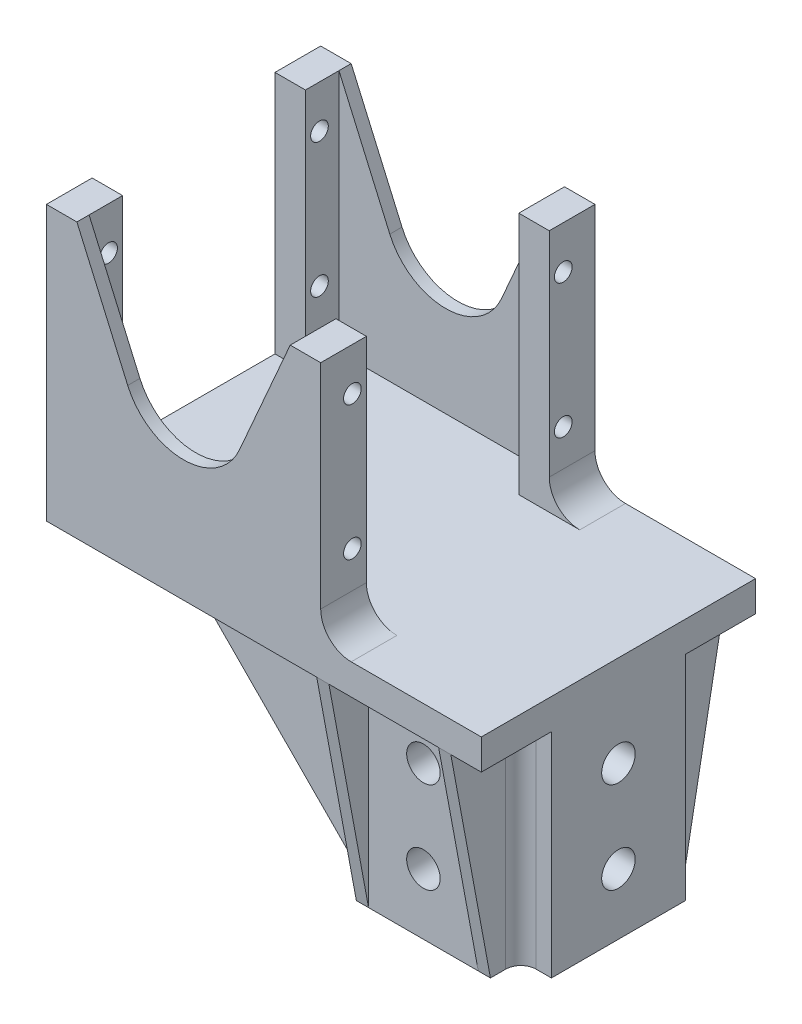
SolidWorks part; units mm, degrees
material "PLA"
ref_plane "Front Plane" through (0, 0, 0) normal (0, 0, 1) x (1, 0, 0)
ref_plane "Top Plane" through (0, 0, 0) normal (0, 1, 0) x (1, 0, 0)
ref_plane "Right Plane" through (0, 0, 0) normal (1, 0, 0) x (0, 0, -1)
sketch "Sketch2" plane through (0, 0, 0) normal (0, 0, 1) x (1, 0, 0)
  line L0 (12.8375, 22.5) -> (17.8375, 22.5) construction
  line L1 (-53.5125, 22.5) -> (17.8375, 22.5) construction
  line L2 (-17.8375, 22.5) -> (-17.8375, -22.5) construction
  line L3 (-53.5125, -22.5) -> (17.8375, -22.5)
  line L4 (17.8375, 22.5) -> (17.8375, -22.5) construction
  line L5 (-17.8375, 22.5) -> (17.8375, -22.5) construction
  line L6 (-17.8375, -22.5) -> (17.8375, 22.5) construction
  line L7 (-48.5125, 22.5) -> (12.8375, 22.5) construction
  line L8 (-17.8375, 22.5) -> (-17.8375, -17.5) construction
  line L9 (-48.5125, -17.5) -> (12.8375, -17.5) construction
  line L10 (12.8375, 22.5) -> (12.8375, -17.5) construction
  line L11 (-17.8375, 22.5) -> (12.8375, -17.5) construction
  line L12 (-17.8375, -17.5) -> (12.8375, 22.5) construction
  line L14 (-17.8375, -17.5) -> (-48.5125, 22.5) construction
  line L15 (-17.8375, 22.5) -> (-48.5125, -17.5) construction
  line L16 (-17.8375, -22.5) -> (-53.5125, 22.5) construction
  line L17 (-17.8375, 22.5) -> (-53.5125, -22.5) construction
  line L18 (-48.5125, 22.5) -> (-48.5125, -17.5)
  line L19 (-53.5125, 22.5) -> (-53.5125, -22.5)
  line L20 (-48.5125, 22.5) -> (-53.5125, 22.5)
  line L22 (-8.5125, -17.5) -> (-8.5125, 22.5)
  line L23 (-8.5125, 22.5) -> (-13.5125, 22.5)
  line L24 (-13.5125, 22.5) -> (-13.5125, -17.5)
  line L26 (17.8375, -17.5) -> (17.8375, -22.5)
  line L27 (-48.5125, -17.5) -> (-13.5125, -17.5)
  line L28 (-8.5125, -17.5) -> (17.8375, -17.5)
  point P4 (0, 0)
  point P8 (-2.5, 2.5)
  point P14 (-33.175, 2.5)
  point P15 (-35.675, 0)
  dimension "D1" = 5
  dimension "D2" = 40
  dimension "D3" = 26.35
  dimension "D4" = 5
  dimension "D5" = 35
  dimension "D6" = 5
extrude "Boss-Extrude1" add sketch "Sketch2" along normal blind 45
sketch "Sketch3" plane through (-53.5125, 0, 0) normal (1, 0, 0) x (0, 0, -1)
  line L0 (-5.2, 22.5) -> (-5.2, -22.5) construction
  line L2 (-39.8, 22.5) -> (-39.8, -22.5) construction
  line L4 (-37.5, 22.5) -> (-7.5, 22.5)
  line L5 (-37.5, 22.5) -> (-37.5, -17.5)
  line L6 (-37.5, -17.5) -> (-7.5, -17.5)
  line L7 (-7.5, 22.5) -> (-7.5, -17.5)
  line L8 (-37.5, 22.5) -> (-7.5, -17.5) construction
  line L9 (-37.5, -17.5) -> (-7.5, 22.5) construction
  line L10 (-45, 22.5) -> (0, 22.5) construction
  line L11 (-39.8, 15.5) -> (-5.2, 15.5) construction
  line L12 (-39.8, -6.5) -> (-5.2, -6.5) construction
  line L13 (-45, -22.5) -> (0, -22.5) construction
  circle A2 centre (-5.2, 15.5) radius 1.25 construction
  circle A3 centre (-5.2, -6.5) radius 1.25 construction
  circle A4 centre (-39.8, 15.5) radius 1.25 construction
  circle A5 centre (-39.8, -6.5) radius 1.25 construction
  point P10 (-22.5, 2.5)
  dimension "D4" = 2.3
  dimension "D7" = 2.5
  dimension "D5" = 2.5
  dimension "D6" = 2.5
  dimension "D9" = 2.5
  dimension "D8" = 22
  dimension "D1" = 30
  dimension "D2" = 5
  dimension "D3" = 2.3
  dimension "D10" = 11
extrude "Cut-Extrude1" cut sketch "Sketch3" along normal through all
sketch "Sketch4" plane through (0, -22.5, 0) normal (0, -1, 0) x (1, 0, 0)
  line L0 (-53.5125, 22.5) -> (17.8375, 22.5) construction
  line L1 (17.8375, 45) -> (17.8375, 0) construction
  line L3 (-53.5125, 45) -> (-53.5125, 0) construction
  line L10 (-8.4125, 32.75) -> (12.0875, 32.75)
  line L11 (-8.4125, 32.75) -> (-8.4125, 12.25)
  line L12 (-8.4125, 12.25) -> (12.0875, 12.25)
  line L13 (12.0875, 32.75) -> (12.0875, 12.25)
  line L14 (-8.4125, 32.75) -> (12.0875, 12.25) construction
  line L15 (-8.4125, 12.25) -> (12.0875, 32.75) construction
  line L16 (-14.1625, 38.5) -> (17.8375, 38.5)
  line L17 (-14.1625, 38.5) -> (-14.1625, 6.5)
  line L18 (-14.1625, 6.5) -> (17.8375, 6.5)
  line L19 (17.8375, 38.5) -> (17.8375, 6.5)
  line L20 (-14.1625, 38.5) -> (17.8375, 6.5) construction
  line L21 (-14.1625, 6.5) -> (17.8375, 38.5) construction
  circle A0 centre (1.8375, 22.5) radius 2.5
  point P18 (1.8375, 22.5)
  point P23 (1.8375, 22.5)
  dimension "D1" = 5
  dimension "D2" = 20.5
  dimension "D3" = 20.5
  dimension "D4" = 32
extrude "Boss-Extrude2" add sketch "Sketch4" along normal blind 35 contours L19 L16 L17 L18 L10 L13 L12 L11 region at (1.8375, -22.5, 38.0475)
sketch "Sketch5" plane through (0, 0, 38.5) normal (0, 0, 1) x (1, 0, 0)
  line L0 (1.8375, -22.5) -> (1.8375, -57.5) construction
  line L3 (-14.1625, -22.5) -> (17.8375, -22.5) construction
  line L4 (-14.1625, -57.5) -> (17.8375, -57.5) construction
  circle A0 centre (1.8375, -32.5) radius 2.5 construction
  circle A1 centre (1.8375, -47.5) radius 2.5 construction
  dimension "D2" = 5
  dimension "D3" = 5
  dimension "D4" = 10
  dimension "D1" = 15
sketch "Sketch6" plane through (0, -57.5, 0) normal (0, -1, 0) x (-1, 0, 0)
  line L1 (14.1625, -38.5) -> (9.1625, -38.5)
  line L2 (14.1625, -38.5) -> (14.1625, -33.5)
  line L3 (14.1625, -33.5) -> (9.1625, -33.5)
  line L4 (9.1625, -38.5) -> (9.1625, -33.5)
  line L5 (14.1625, -38.5) -> (9.1625, -33.5) construction
  line L6 (14.1625, -33.5) -> (9.1625, -38.5) construction
  line L7 (-17.8375, -38.5) -> (-12.8375, -38.5)
  line L8 (-17.8375, -38.5) -> (-17.8375, -33.5)
  line L9 (-17.8375, -33.5) -> (-12.8375, -33.5)
  line L10 (-12.8375, -38.5) -> (-12.8375, -33.5)
  line L11 (-17.8375, -38.5) -> (-12.8375, -33.5) construction
  line L12 (-17.8375, -33.5) -> (-12.8375, -38.5) construction
  line L13 (-17.8375, -6.5) -> (-12.8375, -6.5)
  line L14 (-17.8375, -6.5) -> (-17.8375, -11.5)
  line L15 (-17.8375, -11.5) -> (-12.8375, -11.5)
  line L16 (-12.8375, -6.5) -> (-12.8375, -11.5)
  line L17 (-17.8375, -6.5) -> (-12.8375, -11.5) construction
  line L18 (-17.8375, -11.5) -> (-12.8375, -6.5) construction
  line L19 (14.1625, -6.5) -> (9.1625, -6.5)
  line L20 (14.1625, -6.5) -> (14.1625, -11.5)
  line L21 (14.1625, -11.5) -> (9.1625, -11.5)
  line L22 (9.1625, -6.5) -> (9.1625, -11.5)
  line L23 (14.1625, -6.5) -> (9.1625, -11.5) construction
  line L24 (14.1625, -11.5) -> (9.1625, -6.5) construction
  point P4 (11.6625, -36)
  point P6 (-11.8375, -32.5)
  point P11 (-15.3375, -36)
  point P18 (-15.3375, -9)
  point P25 (11.6625, -9)
  dimension "D1" = 5
  dimension "D2" = 5
  dimension "D3" = 5
  dimension "D4" = 5
extrude "Cut-Extrude4" cut sketch "Sketch6" against normal up to surface (35 mm away) up to face at (-8, -22.5, 22.5)
sketch "Sketch9" plane through (0, 0, 33.5) normal (0, 0, 1) x (1, 0, 0)
  line L0 (-14.1625, -57.5) -> (-48.75, -22.5)
  line L1 (-53.5125, -22.5) -> (17.8375, -22.5) construction
  line L2 (-53.5125, -22.5) -> (17.8375, -22.5) construction
rib "Rib1" sketch "Sketch9" sketch "Sketch9" thickness 2 extrusion direction parallel to sketch draft on no parameters "D1"=2
pattern_linear "LPattern1" count 2 spacing 20 along (0, 0, -1) of "Rib1"
sketch "Sketch14" plane through (12.8375, 0, 0) normal (1, 0, 0) x (0, 0, -1)
  line L0 (-6.5, -57.5) -> (0, -22.5)
rib "Rib6" sketch "Sketch14" sketch "Sketch14" thickness 2 extrusion direction parallel to sketch draft on no parameters "D1"=2
sketch "Sketch15" plane through (-9.1625, 0, 0) normal (-1, 0, 0) x (0, 0, 1)
  line L0 (6.5, -57.5) -> (0, -22.5)
rib "Rib7" sketch "Sketch15" sketch "Sketch15" thickness 2 extrusion direction parallel to sketch draft on no parameters "D1"=2
fillet "Fillet2" radius 5 3 edges at (-14.1625, -22.5, 22.5) (1.8375, -22.5, 6.5) (1.8375, -22.5, 38.5)
fillet "Fillet3" radius 5 2 edges at (-8.5125, -17.5, 3.75) (-8.5125, -17.5, 41.25)
sketch "Sketch17" plane through (0, 0, 45) normal (0, 0, 1) x (1, 0, 0)
  line L0 (-48.5125, 22.5) -> (-31.0125, -17.5)
  line L1 (-13.5125, -17.5) -> (-48.5125, -17.5) construction
rib "Rib10" sketch "Sketch17" sketch "Sketch17" thickness 2 extrusion direction parallel to sketch draft on no parameters "D1"=2
sketch "Sketch18" plane through (0, 0, 45) normal (0, 0, 1) x (1, 0, 0)
  line L0 (-31.0125, -17.5) -> (-13.5125, 22.5)
rib "Rib11" sketch "Sketch18" sketch "Sketch18" thickness 2 extrusion direction parallel to sketch draft on no parameters "D1"=2
fillet "Fillet4" radius 10 1 edges at (-31.0125, -17.5, 44)
pattern_linear "LPattern2" count 2 spacing 43 along (0, 0, -1) of "Fillet4", "Rib11", "Rib10"
hole_wizard "M5 Clearance Hole2" positions "Sketch20" profile "Sketch22" hole size "M5" standard "ISO"
sketch "Sketch20" plane through (0, 0, 38.5) normal (0, 0, 1) x (1, 0, 0)
  point P0 (1.8375, -32.5)
  point P3 (1.8375, -47.5)
sketch "Sketch22" plane through (1.8375, -32.5, 38.5) normal (1, 0, 0) x (0, -1, 0)
  line L0 (0, 0) -> (0, 7.6524)
  line L1 (0, 7.6524) -> (2.75, 6)
  line L2 (2.75, 6) -> (2.75, 0)
  line L5 (2.75, 0) -> (0, 0)
  line L10 (0, 7.6524) -> (-2.75, 6) construction
  line L11 (0, -6.35) -> (0, 107.95) construction
  dimension "Hole Dia." = 5.5
  dimension "Hole Depth" = 6
  dimension "Drill Angle" = 118
hole_wizard "M2.5 Clearance Hole1" positions "Sketch23" profile "Sketch24" hole size "M2.5" standard "ISO" end condition through all
sketch "Sketch23" plane through (-53.5125, 0, 0) normal (-1, 0, 0) x (0, 0, 1)
  point P0 (5.2, 15.5)
  point P3 (39.8, 15.5)
  point P6 (39.8, -6.5)
  point P9 (5.2, -6.5)
sketch "Sketch24" plane through (-53.5125, 15.5, 5.2) normal (0, 1, 0) x (0, 0, 1)
  line L0 (0, 0) -> (0, 71.35)
  line L1 (0, 71.35) -> (1.45, 71.35)
  line L2 (1.45, 71.35) -> (1.45, 0)
  line L5 (1.45, 0) -> (0, 0)
  line L11 (0, -6.35) -> (0, 107.95) construction
  dimension "Thru Hole Dia." = 2.9
  dimension "Thru Hole Depth" = 71.35
fillet "Fillet5" radius 2.5 4 edges at (-9.1625, -40, 11.5) (-9.1625, -40, 33.5) (12.8375, -40, 33.5) (12.8375, -40, 11.5)
extrude "Boss-Extrude4" add sketch "Sketch4<4>" along normal blind 8 contours A0 region at (1.8375, -22.5, 22.5)
sketch "Sketch4<4>" plane through (0, -22.5, 0) normal (0, -1, 0) x (1, 0, 0) same geometry as "Sketch4"
pattern_circular "CirPattern1" count 4 every 90 about axis through (1.8375, -30.5, 22.5) along (0, -1, 0) of "M5 Clearance Hole2"
ref_axis "Axis2" through (1.8375, -30.5, 22.5) along (0, 1, 0)
ref_plane "Plane1" through (0, 0, 22.5) normal (0, 0, 1) x (1, 0, 0)
mirror "Mirror1" about plane through (0, 0, 22.5) normal (0, 0, 1) of "Rib6", "Rib7"
